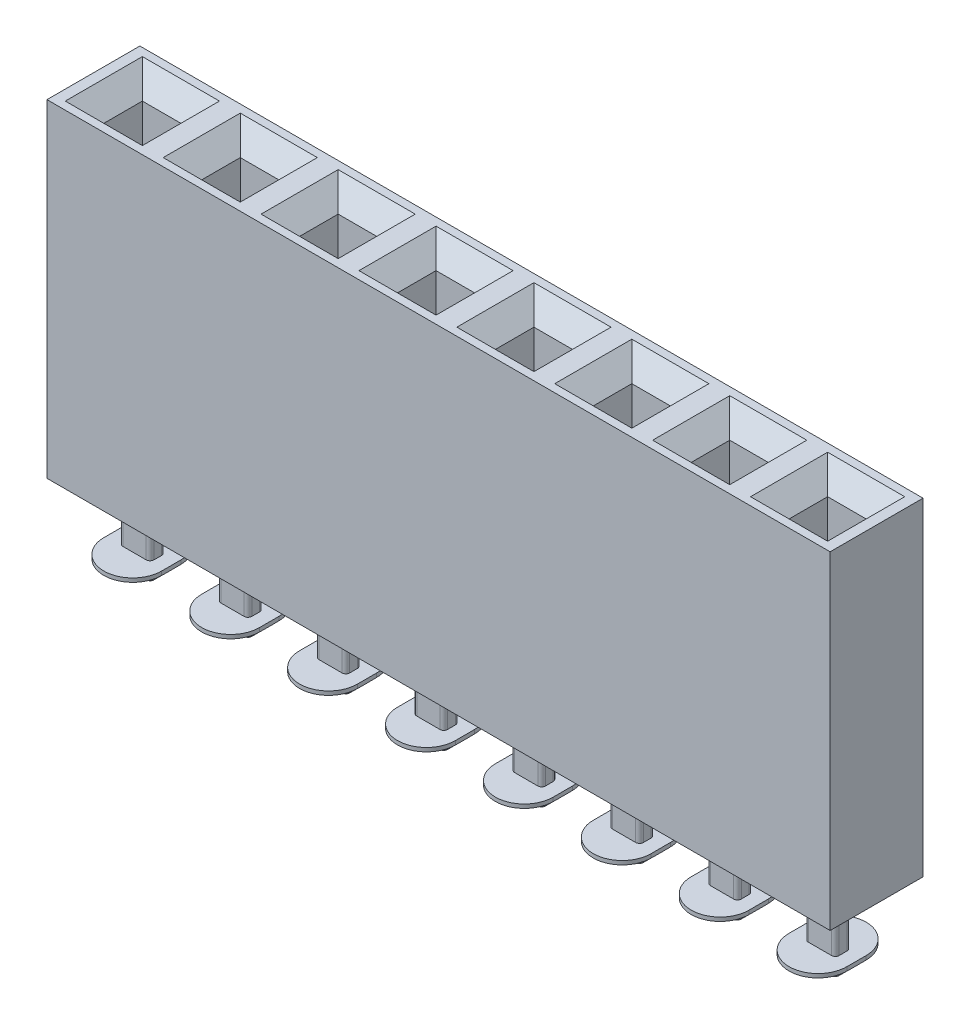
SolidWorks part; units mm, degrees
material "PA Type 6"
ref_plane "Front Plane" through (0, 0, 0) normal (0, 0, 1) x (1, 0, 0)
ref_plane "Top Plane" through (0, 0, 0) normal (0, 1, 0) x (1, 0, 0)
ref_plane "Right Plane" through (0, 0, 0) normal (1, 0, 0) x (0, 0, -1)
ref_plane "Plane1" through (0, -1.65, 0) normal (0, 1, 0) x (1, 0, 0)
sketch "Sketch2" plane through (0, 0, 0) normal (0, 1, 0) x (1, 0, 0)
  line L0 (0, -1.3255) -> (0, 1.3255) construction
  line L1 (-1.27, 1.205) -> (19.05, 1.205)
  line L2 (-1.27, 1.205) -> (-1.27, -1.205)
  line L3 (-1.27, -1.205) -> (19.05, -1.205)
  line L4 (19.05, 1.205) -> (19.05, -1.205)
  line L5 (-4.6805, 0) -> (4.6805, 0) construction
  dimension "D1" = 20.32
  dimension "D2" = 1.27
  dimension "D3" = 2.41
  dimension "D4" = 1.205
extrude "Boss-Extrude1" add sketch "Sketch2" along normal blind 8.51
sketch "Sketch5" plane through (0, 8.51, 0) normal (0, 1, 0) x (1, 0, 0)
  line L0 (-5.7805, 0) -> (5.7805, 0) construction
  line L1 (0.5, 0.5) -> (-0.5, 0.5)
  line L2 (0.5, 0.5) -> (0.5, -0.5)
  line L3 (0.5, -0.5) -> (-0.5, -0.5)
  line L4 (-0.5, 0.5) -> (-0.5, -0.5)
  line L5 (0, -1.3255) -> (0, 1.3255) construction
  dimension "D1" = 0.5
  dimension "D2" = 1
  dimension "D3" = 0.5
extrude "Cut-Extrude1" cut sketch "Sketch5" against normal blind 5
chamfer "Chamfer1" distance 0.5 angle 45 4 edges at (-0.5, 8.51, 0) (0, 8.51, 0.5) (0.5, 8.51, 0) (0, 8.51, -0.5)
pattern_linear "LPattern3" count 8 spacing 2.54 along (1, 0, 0) of "Chamfer1", "Cut-Extrude1"
sketch "Sketch8" plane through (0, 0, 0) normal (0, 1, 0) x (1, 0, 0)
  line L0 (0, -1.3255) -> (0, 1.3255) construction
  line L1 (-0.3, -0.2) -> (0.3, -0.2)
  line L2 (-0.4, -0.1) -> (-0.4, 0.1)
  line L3 (-0.3, 0.2) -> (0.3, 0.2)
  line L4 (0.4, -0.1) -> (0.4, 0.1)
  line L5 (-4.6805, 0) -> (4.6805, 0) construction
  arc A0 (-0.3, -0.2) -> (-0.4, -0.1) centre (-0.3, -0.1) cw
  arc A1 (0.3, -0.2) -> (0.4, -0.1) centre (0.3, -0.1) ccw
  arc A2 (0.3, 0.2) -> (0.4, 0.1) centre (0.3, 0.1) cw
  arc A3 (-0.4, 0.1) -> (-0.3, 0.2) centre (-0.3, 0.1) cw
  point P10 (-0.4, -0.2)
  point P13 (0.4, -0.2)
  point P16 (0.4, 0.2)
  dimension "D5" = 0.1
  dimension "D1" = 0.4
  dimension "D2" = 0.8
  dimension "D3" = 0.4
  dimension "D4" = 0.2
extrude "Boss-Extrude2" add sketch "Sketch8" against normal blind 2 separate body
sketch "Sketch10" plane through (0, -1.65, 0) normal (0, 1, 0) x (1, 0, 0)
  line L0 (0, -0.25) -> (0, 0.25) construction
  line L1 (0, -1.3255) -> (0, 1.3255) construction
  line L2 (-0.75, -0.25) -> (-0.75, 0.25)
  line L3 (0.75, -0.25) -> (0.75, 0.25)
  line L4 (-5.7805, 0) -> (5.7805, 0) construction
  arc A0 (-0.75, -0.25) -> (0.75, -0.25) centre (0, -0.25) ccw
  arc A1 (0.75, 0.25) -> (-0.75, 0.25) centre (0, 0.25) ccw
  point P5 (0, 0)
  dimension "D1" = 1.5
  dimension "D2" = 0.5
extrude "Boss-Extrude3" add sketch "Sketch10" along normal blind 0.1
fillet "Fillet2" radius 0.4 6 edges at (-0.3707, -1.65, -0.1707) (-0.3707, -1.65, 0.1707) (0, -1.65, 0.2) (0.3707, -1.65, 0.1707) (0.3707, -1.65, -0.1707) (0, -1.65, -0.2)
ref_axis "Axis1" through (0, -2.5255, 0) along (0, 1, 0)
pattern_linear "Répétition linéaire1" count 8 spacing 2.54 along (1, 0, 0) of bodies 105
equation "\"D1@Sketch2\"=2.54 * 8"
